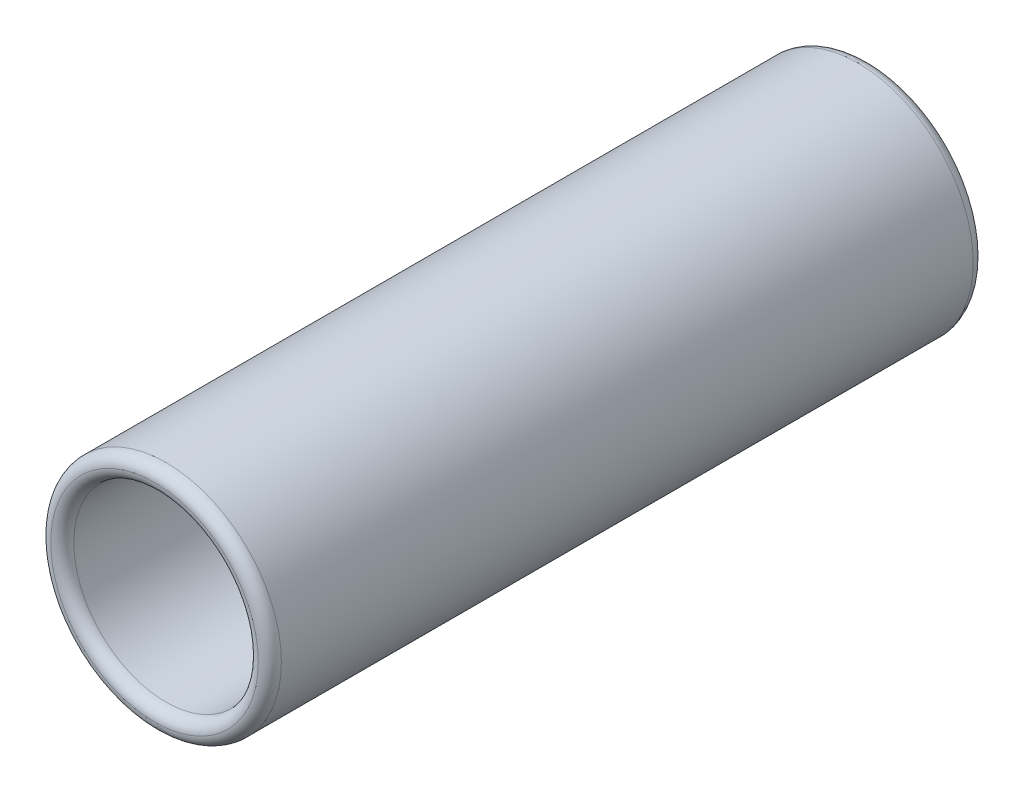
SolidWorks part; units mm, degrees
ref_plane "Front Plane" through (0, 0, 0) normal (0, 0, 1) x (1, 0, 0)
ref_plane "Top Plane" through (0, 0, 0) normal (0, 1, 0) x (1, 0, 0)
ref_plane "Right Plane" through (0, 0, 0) normal (1, 0, 0) x (0, 0, -1)
sketch "Sketch1" plane through (0, 0, 0) normal (0, 0, 1) x (1, 0, 0)
  circle A0 centre (0, 0) radius 0.5
extrude "Boss-Extrude1" add sketch "Sketch1" along normal blind 3.1
sketch "Sketch2" plane through (0, 0, 3.1) normal (0, 0, 1) x (1, 0, 0)
  circle A0 centre (0, 0) radius 0.4
extrude "Cut-Extrude1" cut sketch "Sketch2" against normal blind 3.1
fillet "Fillet1" radius 0.05 1 edges at (0.5, 0, 3.1) type face fillet first side face at (0.4, 0, 3.1) second side face at (0.5, 0, 3.1)
fillet "Fillet2" radius 0.05 1 edges at (0.4, 0, 3.1) type face fillet first side face at (0.4, 0, 0) second side face at (0.45, 0, 3.1)
fillet "Fillet3" radius 0.05 1 edges at (0.5, 0, 0) type face fillet first side face at (0.5, 0, 3.05) second side face at (0.4, 0, 0)
fillet "Fillet4" radius 0.05 1 edges at (0.4, 0, 0) type face fillet first side face at (0.4, 0, 3.05) second side face at (0.45, 0, 0)
